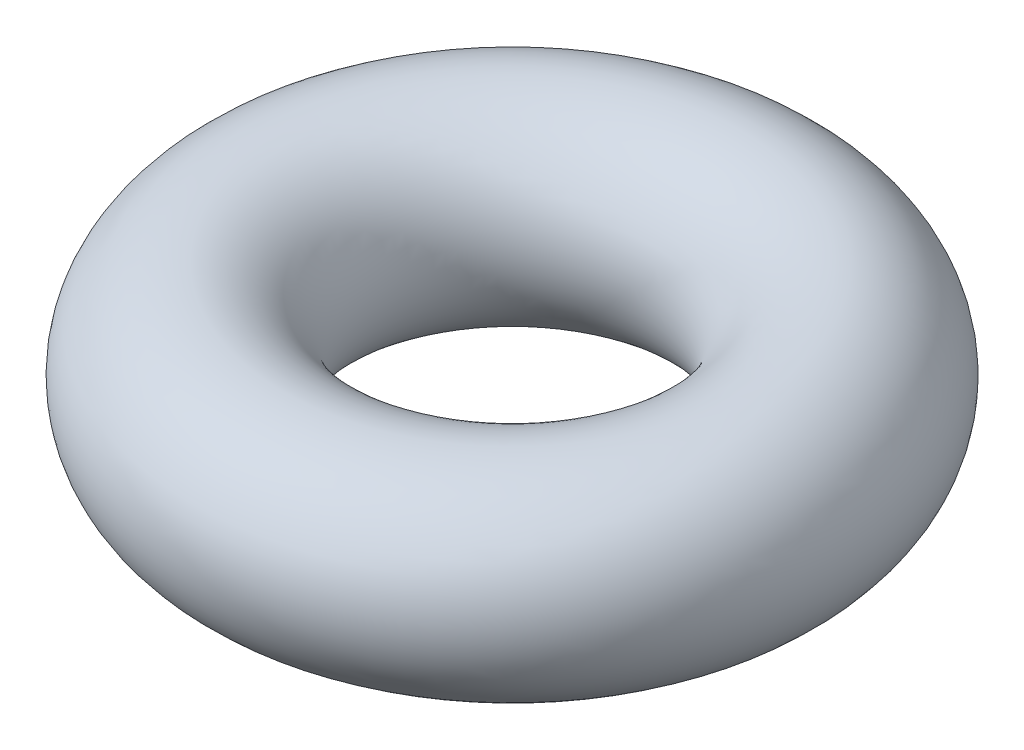
SolidWorks part; units mm, degrees
material "Silicon Rubber"
ref_plane "Front Plane" through (0, 0, 0) normal (0, 0, 1) x (1, 0, 0)
ref_plane "Top Plane" through (0, 0, 0) normal (0, 1, 0) x (1, 0, 0)
ref_plane "Right Plane" through (0, 0, 0) normal (1, 0, 0) x (0, 0, -1)
ref_axis "CentralAxis" through (0, 0.55, 0) along (0, -1, 0)
sketch "MainBodyS" plane through (0, 0, 0) normal (0, 0, 1) x (1, 0, 0)
  line L0 (0, 0) -> (1.75, 0) construction
  line L1 (0, 0) -> (0, -1) construction
  circle A0 centre (1.75, 0) radius 0.75
  point P3 (2.5, 0)
  point P6 (-2.5, 0)
  point P7 (-1, 0)
  point P8 (1, 0)
  dimension "Dia" = 1.5
  dimension "RefRevolve" = 1
  dimension "RevolveDia" = 3.5
  dimension "OD" = 5
  dimension "ID" = 2
revolve "MAIN BODY" add sketch "MainBodyS" angle 360 about L1
